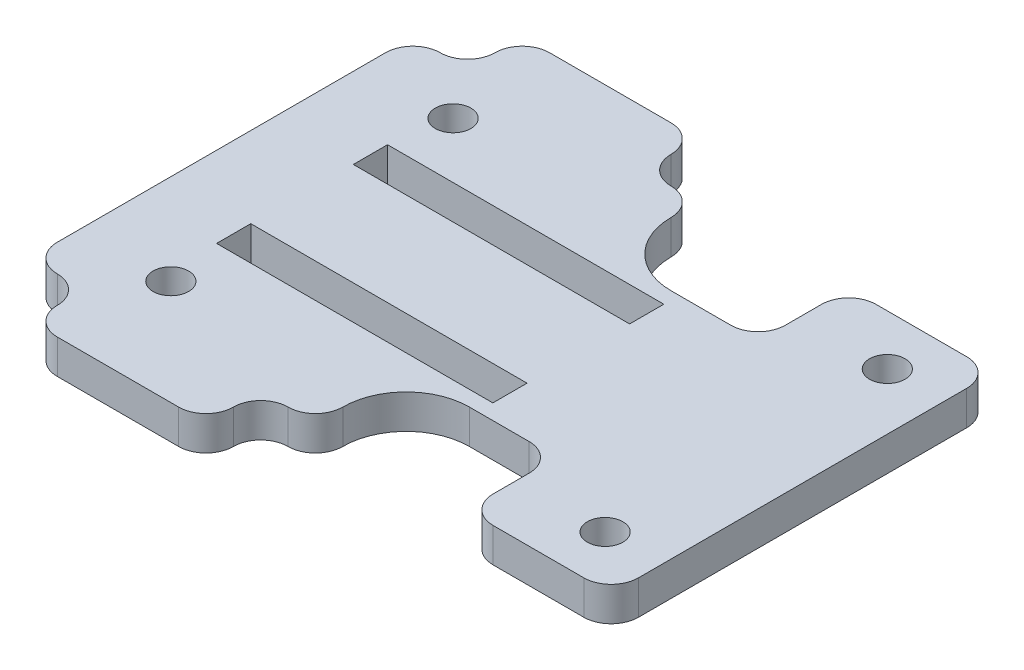
SolidWorks part; units mm, degrees
other "下垫片"
ref_plane "前视基准面" through (0, 0, 0) normal (0, 0, 1) x (1, 0, 0)
ref_plane "上视基准面" through (0, 0, 0) normal (0, 1, 0) x (1, 0, 0)
ref_plane "右视基准面" through (0, 0, 0) normal (1, 0, 0) x (0, 0, -1)
other "Configuration Table"
sketch "草图1" plane through (0, 0, 0) normal (0, 1, 0) x (1, 0, 0)
  line L0 (-89.3251, 0) -> (102.0425, 0) construction
  line L1 (0, 56.7239) -> (0, -62.578) construction
  line L2 (-33.2, -7.5) -> (7.2, -7.5)
  line L3 (-33.2, 12.5) -> (7.2, 12.5)
  line L4 (-33.2, 12.5) -> (-33.2, 7.5)
  line L5 (-33.2, 7.5) -> (7.2, 7.5)
  line L6 (7.2, 12.5) -> (7.2, 7.5)
  line L7 (-33.2, 12.5) -> (7.2, 7.5) construction
  line L8 (-33.2, 7.5) -> (7.2, 12.5) construction
  line L9 (7.2, -12.5) -> (7.2, -7.5)
  line L10 (-33.2, -12.5) -> (7.2, -12.5)
  line L11 (-33.2, -12.5) -> (-33.2, -7.5)
  line L14 (-3.25, -26.5375) -> (-3.25, -14.7375)
  line L15 (-3.25, -14.7375) -> (18.75, -14.7375)
  line L16 (18.75, -26.5375) -> (18.75, -14.7375)
  line L17 (-3.25, -26.5375) -> (18.75, -14.7375) construction
  line L18 (-3.25, -14.7375) -> (18.75, -26.5375) construction
  line L19 (-3.25, 14.7375) -> (18.75, 14.7375)
  line L20 (18.75, 26.5375) -> (18.75, 14.7375)
  line L22 (-3.25, 26.5375) -> (-3.25, 14.7375)
  line L23 (-3.25, 29.8695) -> (18.75, 29.8695)
  line L25 (-3.25, -26.5375) -> (-3.25, -29.8695)
  line L26 (-3.25, -29.8695) -> (18.75, -29.8695)
  line L27 (18.75, -26.5375) -> (18.75, -29.8695)
  line L28 (18.75, 26.5375) -> (18.75, 29.8695)
  line L30 (-3.25, 26.5375) -> (-3.25, 29.8695)
  circle A0 centre (-31.75, 20.6375) radius 2.6
  circle A4 centre (31.75, 20.6375) radius 2.6
  circle A5 centre (31.75, -20.6375) radius 2.6
  circle A6 centre (-31.75, -20.6375) radius 2.6
  point P13 (-13, 10)
  point P22 (7.75, -20.6375)
  point P35 (-13, 10)
  dimension "D5" = 5.2
  dimension "D11" = 5.2
  dimension "D1" = 40.4
  dimension "D2" = 31.75
  dimension "D3" = 5
  dimension "D4" = 20.6375
  dimension "D6" = 11.8
  dimension "D7" = 22
  dimension "D8" = 11.8
  dimension "D9" = 0
  dimension "D10" = 13
  dimension "D12" = 5
  dimension "D13" = 40.4
  dimension "D14" = 13
  dimension "D15" = 10
  dimension "D16" = 2.2375
sketch "草图3" plane through (0, 0, 0) normal (0, 1, 0) x (1, 0, 0)
  line L0 (-55, 0) -> (55, 0) construction
  line L1 (-11.25, -28) -> (40, -28)
  line L3 (-11.25, 28) -> (40, 28)
  line L4 (40, -28) -> (40, 28)
  line L5 (-40, -28) -> (40, 28) construction
  line L6 (-40, 28) -> (40, -28) construction
  line L10 (-45, 28) -> (-45, -28)
  line L15 (-11.25, 28) -> (-11.25, 36)
  line L16 (-37, 36) -> (-11.25, 36)
  line L18 (-45, 28) -> (-37, 28)
  line L19 (-37, 28) -> (-37, 36)
  line L20 (-11.25, -28) -> (-11.25, -36)
  line L21 (-37, -36) -> (-11.25, -36)
  line L22 (-37, -28) -> (-37, -36)
  line L23 (-45, -28) -> (-37, -28)
  point P0 (0, 0)
  dimension "D1" = 56
  dimension "D2" = 80
  dimension "D3" = 5
  dimension "D4" = 8
  dimension "D5" = 25.75
  dimension "D6" = 8
extrude "凸台-拉伸1" add sketch "草图3" along normal blind 5
extrude "切除-拉伸1" cut sketch "草图1" along normal up to surface (5 mm away) up to face at (-16.9167, 5, 0)
fillet "圆角2" radius 4 18 edges at (-3.25, 2.5, -28) (18.75, 2.5, -28) (40, 2.5, -28) (40, 2.5, 28) (18.75, 2.5, 28) (-3.25, 2.5, 28) (18.75, 2.5, -14.7375) (18.75, 2.5, 14.7375) (-11.25, 2.5, 28) (-11.25, 2.5, 36) (-11.25, 2.5, -36) (-11.25, 2.5, -28) (-37, 2.5, 36) (-37, 2.5, 28) (-45, 2.5, 28) (-45, 2.5, -28) (-37, 2.5, -28) (-37, 2.5, -36)
fillet "圆角3" radius 9.2625 2 edges at (-3.25, 2.5, -14.7375) (-3.25, 2.5, 14.7375)
